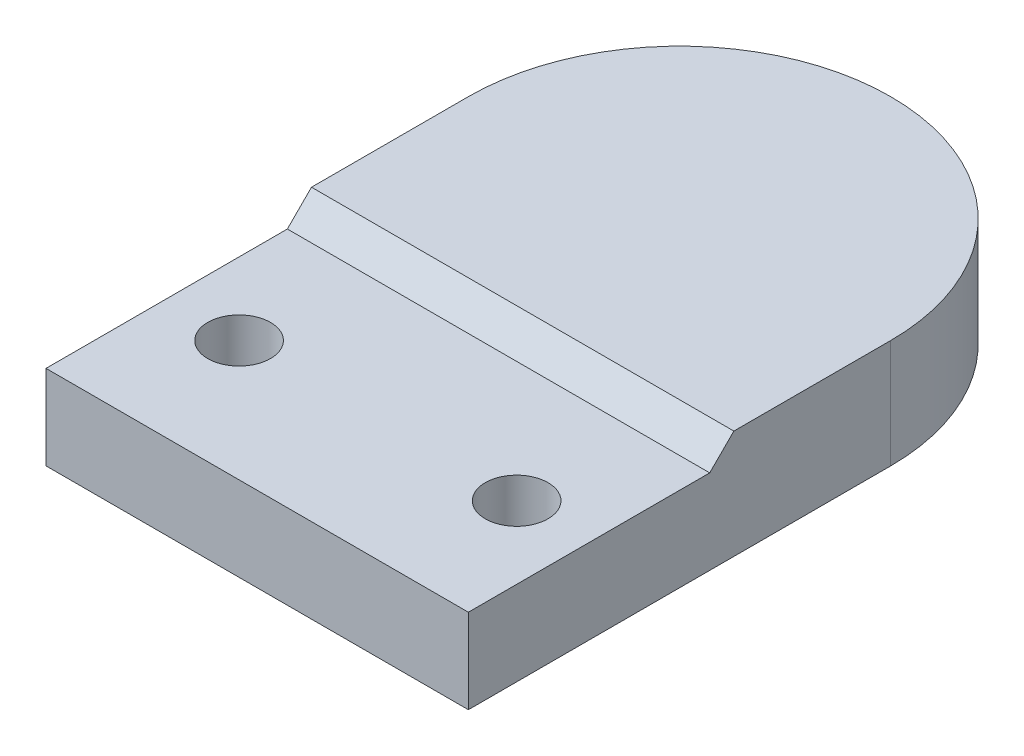
SolidWorks part; units mm, degrees
material "PET"
ref_plane "Front Plane" through (0, 0, 0) normal (0, 0, 1) x (1, 0, 0)
ref_plane "Top Plane" through (0, 0, 0) normal (0, 1, 0) x (1, 0, 0)
ref_plane "Right Plane" through (0, 0, 0) normal (1, 0, 0) x (0, 0, -1)
sketch "Sketch1" plane through (0, 0, 0) normal (0, 1, 0) x (1, 0, 0)
  line L5 (-17.5, 0) -> (-17.5, -15)
  line L6 (17.5, 0) -> (17.5, -15)
  line L9 (-17.5, -15) -> (17.5, -15)
  circle A0 centre (0, 0) radius 11.1
  arc A1 (17.5, 0) -> (-17.5, 0) centre (0, 0) ccw
  dimension "D1" = 22.2
  dimension "D2" = 35
  dimension "D3" = 15
extrude "Boss-Extrude1" add sketch "Sketch1" along normal blind 7
sketch "Sketch4" plane through (0, 0, 0) normal (0, 1, 0) x (1, 0, 0)
  line L0 (-17.5, -15) -> (17.5, -15) construction
  line L1 (-17.5, -15) -> (17.5, -15)
  line L2 (-17.5, -15) -> (-17.5, -35)
  line L3 (-17.5, -35) -> (17.5, -35)
  line L4 (17.5, -15) -> (17.5, -35)
  line L5 (-17.5, 0) -> (-17.5, -15) construction
  point P6 (0, -15)
  dimension "D1" = 20
extrude "Boss-Extrude3" add sketch "Sketch4" along normal blind 7
sketch "Sketch5" plane through (0, 7, 0) normal (0, 1, 0) x (1, 0, 0)
  line L0 (-17.5, -35) -> (17.5, -35) construction
  line L1 (-17.5, 0) -> (-17.5, -35) construction
  line L2 (17.5, -35) -> (17.5, 0) construction
  circle A0 centre (-11.5, -25) radius 2.6
  circle A1 centre (11.5, -25) radius 2.6
  dimension "D1" = 5.2
  dimension "D2" = 5.2
  dimension "D3" = 10
  dimension "D4" = 10
  dimension "D5" = 6
  dimension "D6" = 6
extrude "Cut-Extrude1" cut sketch "Sketch5" against normal through all
sketch "Sketch8" plane through (0, 7, 0) normal (0, 1, 0) x (1, 0, 0)
  line L0 (-17.5, -35) -> (17.5, -35) construction
  line L5 (-17.5, 0) -> (-17.5, -15)
  line L6 (17.5, 0) -> (17.5, -15)
  line L9 (-17.5, -15) -> (17.5, -15)
  arc A1 (17.5, 0) -> (-17.5, 0) centre (0, 0) ccw
  point P1 (-7.182, -17.9775)
  point P2 (0, 0)
  point P3 (-18.1123, -19.0928)
  point P4 (-17.5, -16.416)
  point P5 (0, 0)
  point P6 (0, 0)
  point P7 (-8.9665, -15.9698)
  dimension "D1" = 20
  dimension "D2" = 35
extrude "Boss-Extrude4" add sketch "Sketch8" along normal blind 2
chamfer "Chamfer1" distance 2 angle 45 1 edges at (0, 9, 15)
equation "\"tolerance\"= 0.2"
equation "\"D1@Sketch1\"=\"tolerance\"+22"
equation "\"D1@Sketch5\"=\"tolerance\"+5"
equation "\"D2@Sketch5\"=\"tolerance\"+5"
